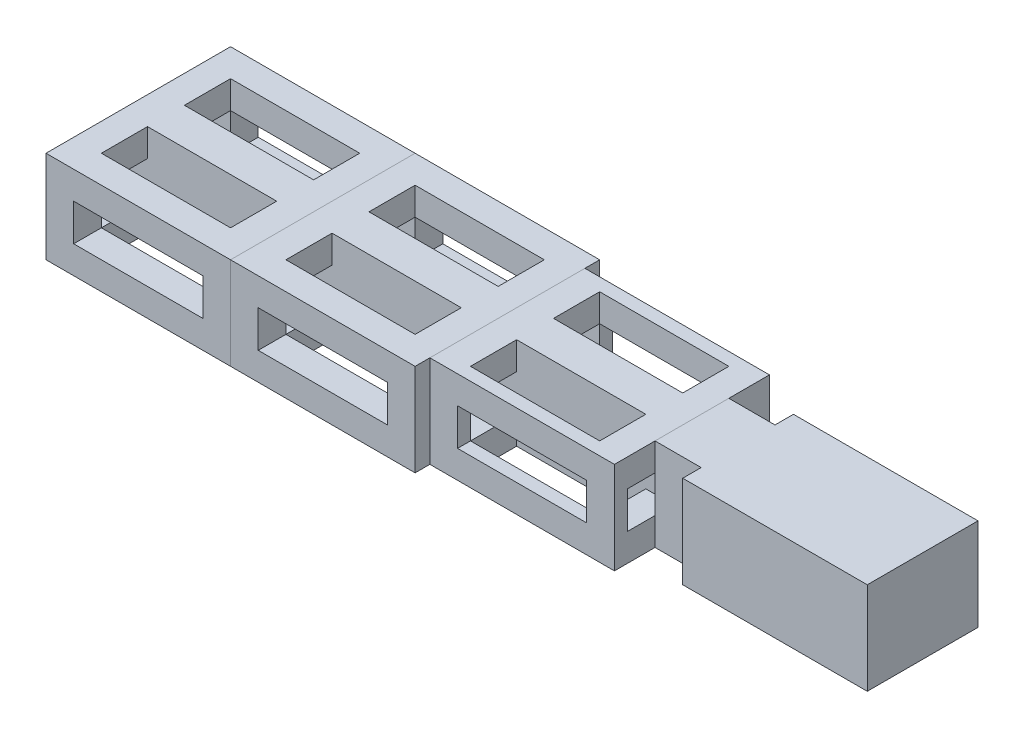
SolidWorks part; units mm, degrees
ref_plane "前视基准面" through (0, 0, 0) normal (0, 0, 1) x (1, 0, 0)
ref_plane "上视基准面" through (0, 0, 0) normal (0, 1, 0) x (1, 0, 0)
ref_plane "右视基准面" through (0, 0, 0) normal (1, 0, 0) x (0, 0, -1)
other "Configuration Table"
sketch "草图1" plane through (0, 0, 0) normal (0, 1, 0) x (1, 0, 0)
  line L0 (10, -10) -> (-10, -10)
  line L1 (10, -10) -> (10, 10)
  line L2 (-10, -10) -> (-10, 10)
  line L3 (10, 10) -> (-10, 10)
  line L4 (10, -10) -> (-10, 10) construction
  line L5 (-10, -10) -> (10, 10) construction
  line L6 (10, 10) -> (10, -10)
  line L7 (10, 10) -> (30, 10)
  line L8 (10, -10) -> (30, -10)
  line L9 (30, 10) -> (30, -10)
  line L10 (-10, -10) -> (-10, 10)
  line L11 (-10, -10) -> (-30, -10)
  line L12 (-10, 10) -> (-30, 10)
  line L13 (-30, -10) -> (-30, 10)
  point P1 (0, 0)
  dimension "D1" = 20
  dimension "D2" = 20
  dimension "D3" = 20
  dimension "D4" = 20
extrude "凸台-拉伸1" add sketch "草图1" along normal blind 10 contours L13 L11 L2 L12 region at (-20, 0, 0)
extrude "凸台-拉伸2" add sketch "草图1<3>" along normal blind 10 separate body contours L1 L3 L2 L0 region at (0, 0, 0)
sketch "草图1<3>" plane through (0, 0, 0) normal (0, 1, 0) x (1, 0, 0) same geometry as "草图1"
extrude "凸台-拉伸3" add sketch "草图1<4>" along normal blind 10 separate body contours L9 L7 L1 L8 region at (20, 0, 0)
sketch "草图1<4>" plane through (0, 0, 0) normal (0, 1, 0) x (1, 0, 0) same geometry as "草图1"
fillet "圆角1" [suppressed] radius 2
fillet "圆角2" [suppressed] radius 2
fillet "圆角3" [suppressed] radius 2
fillet "圆角4" [suppressed] radius 2
fillet "圆角5" [suppressed] radius 2
sketch "草图2" plane through (-30, 0, 0) normal (-1, 0, 0) x (0, 0, 1)
  line L0 (-10, 5) -> (10, 5) construction
  line L1 (-10, 10) -> (-10, 0) construction
  line L2 (10, 10) -> (10, 0) construction
  line L3 (0, 10) -> (0, 0) construction
  line L4 (10, 10) -> (-10, 10) construction
  line L6 (-7, 7) -> (7, 7)
  line L7 (-7, 7) -> (-7, 3)
  line L8 (-7, 3) -> (7, 3)
  line L9 (7, 7) -> (7, 3)
  line L10 (-7, 7) -> (7, 3) construction
  line L11 (-7, 3) -> (7, 7) construction
  point P11 (0, 5)
  dimension "D1" = 3
  dimension "D2" = 3
extrude "切除-拉伸1" cut sketch "草图2" against normal through all
sketch "草图3" plane through (0, 0, -10) normal (0, 0, -1) x (-1, 0, 0)
  line L8 (-27, 3) -> (-13, 3)
  line L9 (-13, 3) -> (-13, 7)
  line L10 (-13, 7) -> (-27, 7)
  line L11 (-27, 7) -> (-27, 3)
  line L12 (-27, 3) -> (-13, 3)
  line L13 (-13, 3) -> (-13, 7)
  line L14 (-13, 7) -> (-27, 7)
  line L15 (-27, 7) -> (-27, 3)
  line L21 (13, 3) -> (27, 3)
  line L25 (27, 3) -> (27, 7)
  line L26 (7, 3) -> (7, 7)
  line L27 (7, 7) -> (-7, 7)
  line L28 (-7, 7) -> (-7, 3)
  line L29 (-7, 3) -> (7, 3)
  line L30 (7, 3) -> (7, 7)
  line L31 (7, 7) -> (-7, 7)
  line L32 (-7, 7) -> (-7, 3)
  line L33 (-7, 3) -> (7, 3)
  line L34 (27, 7) -> (13, 7)
  line L35 (13, 7) -> (13, 3)
  line L36 (13, 3) -> (27, 3)
  line L37 (27, 3) -> (27, 7)
  line L38 (27, 7) -> (13, 7)
  line L39 (13, 7) -> (13, 3)
  dimension "D1" = 3
  dimension "D2" = 3
  dimension "D3" = 3
extrude "切除-拉伸2" cut sketch "草图3" against normal through all
sketch "草图4" plane through (0, 10, 0) normal (0, 1, 0) x (1, 0, 0)
  line L8 (-27, 7) -> (-27, -7)
  line L9 (-27, -7) -> (-13, -7)
  line L10 (-13, -7) -> (-13, 7)
  line L11 (-13, 7) -> (-27, 7)
  line L12 (-27, 7) -> (-27, -7)
  line L13 (-27, -7) -> (-13, -7)
  line L14 (-13, -7) -> (-13, 7)
  line L15 (-13, 7) -> (-27, 7)
  line L20 (7, -7) -> (7, 7)
  line L21 (7, 7) -> (-7, 7)
  line L22 (-7, 7) -> (-7, -7)
  line L23 (-7, -7) -> (7, -7)
  line L24 (7, -7) -> (7, 7)
  line L25 (7, 7) -> (-7, 7)
  line L26 (-7, 7) -> (-7, -7)
  line L27 (-7, -7) -> (7, -7)
  line L32 (27, -7) -> (27, 7)
  line L33 (27, 7) -> (13, 7)
  line L34 (13, 7) -> (13, -7)
  line L35 (13, -7) -> (27, -7)
  line L36 (27, -7) -> (27, 7)
  line L37 (27, 7) -> (13, 7)
  line L38 (13, 7) -> (13, -7)
  line L39 (13, -7) -> (27, -7)
  dimension "D1" = 3
  dimension "D2" = 3
  dimension "D3" = 3
extrude "切除-拉伸3" cut sketch "草图4" against normal through all
sketch "草图5" plane through (0, 0, 0) normal (0, 0, 1) x (1, 0, 0)
  line L0 (-10, 5) -> (45, 5) construction
  line L1 (-10, 10) -> (-10, 0) construction
  line L2 (30, 10) -> (30, 0) construction
  line L3 (35, 10) -> (55, 10)
  line L4 (35, 10) -> (35, 0)
  line L5 (35, 0) -> (55, 0)
  line L6 (55, 10) -> (55, 0)
  line L7 (35, 10) -> (55, 0) construction
  line L8 (35, 0) -> (55, 10) construction
  dimension "D1" = 20
  dimension "D2" = 10
  dimension "D3" = 5
extrude "凸台-拉伸4" add sketch "草图5" along normal blind 10 and the other way blind 10 separate body
sketch "草图6" plane through (35, 0, 0) normal (-1, 0, 0) x (0, 0, 1)
  line L0 (-10, 5) -> (10, 5) construction
  line L1 (-10, 10) -> (-10, 0) construction
  line L2 (10, 10) -> (10, 0) construction
  line L3 (10, 10) -> (-10, 10) construction
  line L4 (-4, 10) -> (4, 10)
  line L5 (-4, 10) -> (-4, 0)
  line L6 (-4, 0) -> (4, 0)
  line L7 (4, 10) -> (4, 0)
  line L8 (-4, 10) -> (4, 0) construction
  line L9 (-4, 0) -> (4, 10) construction
  point P6 (0, 5)
  dimension "D1" = 8
extrude "凸台-拉伸5" add sketch "草图6" along normal up to surface (5 mm away) up to face at (30, 5, 0)
sketch "草图7" plane through (0, 0, -10) normal (0, 0, -1) x (-1, 0, 0)
  line L0 (-30, 10) -> (-10, 10)
  line L1 (-30, 10) -> (-30, 0)
  line L2 (-10, 10) -> (-10, 0)
  line L3 (-30, 0) -> (-10, 0)
  line L4 (-10, 0) -> (-30, 0) construction
extrude "切除-拉伸4" cut sketch "草图7" against normal blind 1.6
extrude "切除-拉伸5" cut sketch "草图7<2>" along normal blind 1.6 from surface starting at face at (20, 5, 10)
sketch "草图7<2>" plane through (0, 0, -10) normal (0, 0, -1) x (-1, 0, 0) same geometry as "草图7"
sketch "草图8" plane through (0, 0, -10) normal (0, 0, -1) x (-1, 0, 0)
  line L4 (-55, 10) -> (-55, 0)
  line L5 (-55, 0) -> (-35, 0)
  line L6 (-35, 0) -> (-35, 10)
  line L7 (-35, 10) -> (-55, 10)
  line L8 (-55, 10) -> (-55, 0)
  line L9 (-55, 0) -> (-35, 0)
  line L10 (-35, 0) -> (-35, 10)
  line L11 (-35, 10) -> (-55, 10)
  dimension "D1" = 0
extrude "切除-拉伸6" cut sketch "草图8" against normal blind 4
extrude "切除-拉伸9" cut sketch "草图8<2>" along normal blind 4 from surface starting at face at (45, 5, 10)
sketch "草图8<2>" plane through (0, 0, -10) normal (0, 0, -1) x (-1, 0, 0) same geometry as "草图8"
sketch "草图9" plane through (30, 0, 0) normal (-1, 0, 0) x (0, 0, 1)
  line L0 (-2, 10) -> (2, 10)
  line L1 (-2, 10) -> (-2, 0)
  line L2 (2, 10) -> (2, 0)
  line L3 (-2, 0) -> (2, 0)
  line L4 (10, 10) -> (-10, 10) construction
  line L5 (0, 0) -> (0, 11.8408) construction
  point P9 (2, 5)
  dimension "D1" = 4
extrude "凸台-拉伸6" add sketch "草图9" along normal up to surface (20 mm away) up to face at (10, 5, 0)
sketch "草图10" plane through (10, 0, 0) normal (1, 0, 0) x (0, 0, -1)
  line L0 (-2, 10) -> (2, 10)
  line L1 (-2, 10) -> (-2, 0)
  line L2 (2, 10) -> (2, 0)
  line L3 (-2, 0) -> (2, 0)
  line L4 (6, 10) -> (-6, 10) construction
  line L5 (6, 0) -> (-6, 0) construction
  line L6 (0, 0) -> (0, 11.8044) construction
  dimension "D1" = 4
extrude "凸台-拉伸7" add sketch "草图10" against normal blind 20 from surface starting at face at (10, 5, 0)
sketch "草图11" plane through (-30, 0, 0) normal (-1, 0, 0) x (0, 0, 1)
  line L0 (0, 0) -> (0, 10) construction
  line L1 (10, 0) -> (-10, 0) construction
  line L2 (10, 10) -> (-10, 10) construction
  line L4 (-2, 10) -> (2, 10)
  line L5 (-2, 10) -> (-2, 0)
  line L6 (-2, 0) -> (2, 0)
  line L7 (2, 10) -> (2, 0)
  dimension "D1" = 4
extrude "凸台-拉伸8" add sketch "草图11" against normal blind 20
equation "\"D3@草图1\"=\"D1@草图1\""
equation "\"D4@草图1\"=\"D1@草图1\""
equation "\"D2@草图4\"=\"D1@草图4\""
equation "\"D3@草图4\"=\"D1@草图4\""
